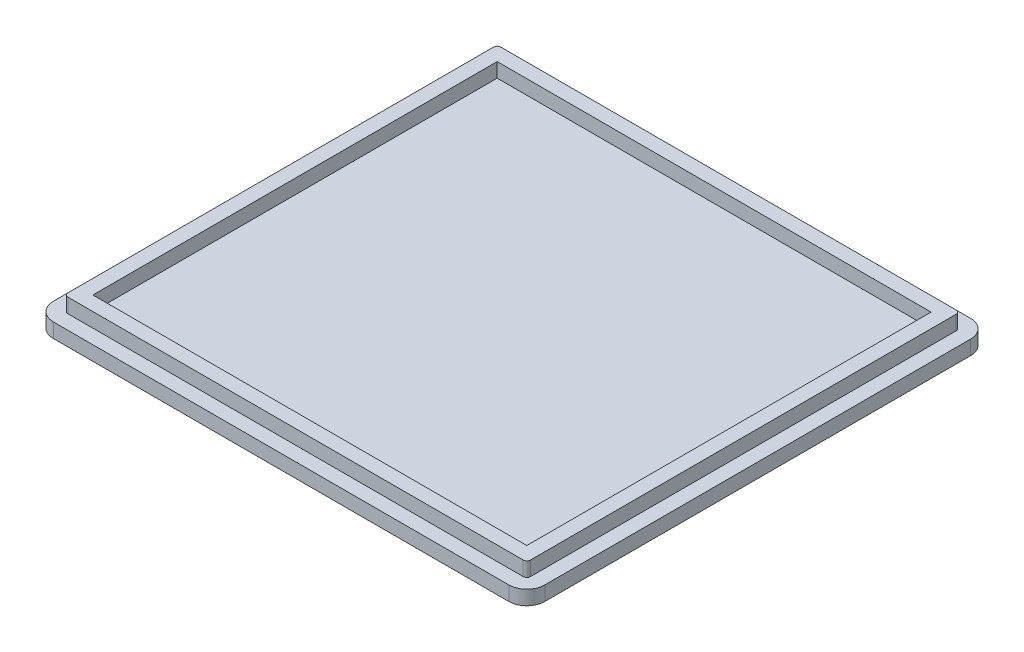
SolidWorks part; units mm, degrees
ref_plane "Front Plane" through (0, 0, 0) normal (0, 0, 1) x (1, 0, 0)
ref_plane "Top Plane" through (0, 0, 0) normal (0, 1, 0) x (1, 0, 0)
ref_plane "Right Plane" through (0, 0, 0) normal (1, 0, 0) x (0, 0, -1)
sketch "Sketch1" plane through (0, 0, 0) normal (0, 1, 0) x (1, 0, 0)
  line L0 (-25.75, 24.1) -> (25.75, 24.1)
  line L1 (-24.15, -22.5) -> (24.15, -22.5)
  line L2 (-24.15, -22.5) -> (-24.15, 22.5)
  line L3 (-24.15, 22.5) -> (24.15, 22.5)
  line L4 (24.15, -22.5) -> (24.15, 22.5)
  line L5 (-24.15, -22.5) -> (24.15, 22.5) construction
  line L6 (-24.15, 22.5) -> (24.15, -22.5) construction
  line L7 (-27.35, -25.7) -> (27.35, -25.7)
  line L8 (-27.35, -25.7) -> (-27.35, 25.7)
  line L9 (-27.35, 25.7) -> (27.35, 25.7)
  line L10 (27.35, -25.7) -> (27.35, 25.7)
  line L11 (-27.35, -25.7) -> (27.35, 25.7) construction
  line L12 (-27.35, 25.7) -> (27.35, -25.7) construction
  line L13 (25.75, -24.1) -> (25.75, 24.1)
  line L14 (-25.75, -24.1) -> (25.75, -24.1)
  line L15 (-25.75, -24.1) -> (-25.75, 24.1)
  point P0 (0, 0)
  point P6 (0, 0)
  dimension "D1" = 48.3
  dimension "D2" = 45
  dimension "D3" = 54.7
  dimension "D4" = 51.4
  dimension "D5" = 1.6
extrude "Boss-Extrude1" add sketch "Sketch1" along normal blind 1.6 contours L7 L10 L9 L8 L14 L15 L0 L13 | L15 L14 L13 L0 L4 L1 L2 L3 | L1 L4 L3 L2 region at (0, 0, -23.3946) region at (0, 0, 0) region at (-26.5994, 0, 0)
extrude "Boss-Extrude2" add sketch "Sketch1<3>" along normal blind 3.2 contours L15 L14 L13 L0 L4 L1 L2 L3 region at (0, 0, -23.3946)
sketch "Sketch1<3>" plane through (0, 0, 0) normal (0, 1, 0) x (1, 0, 0) same geometry as "Sketch1"
fillet "Fillet1" radius 2 4 edges at (-27.35, 0.8, 25.7) (27.35, 0.8, 25.7) (-27.35, 0.8, -25.7) (27.35, 0.8, -25.7)
fillet "Fillet2" radius 0.4 4 edges at (25.75, 2.4, -24.1) (25.75, 2.4, 24.1) (-25.75, 2.4, 24.1) (-25.75, 2.4, -24.1)
